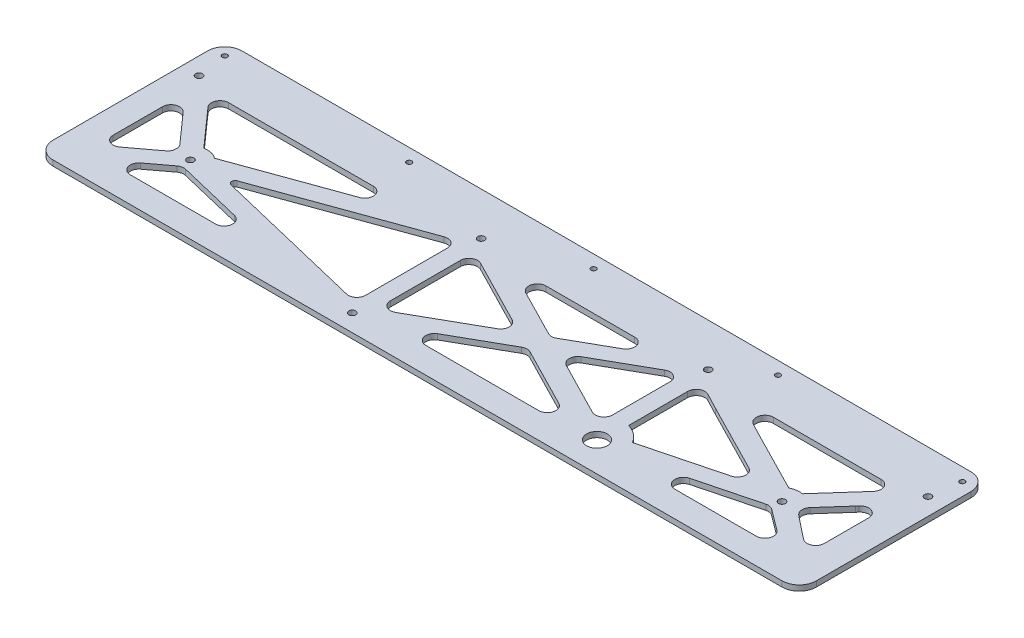
SolidWorks part; units mm, degrees
ref_plane "Front" through (0, 0, 0) normal (0, 0, 1) x (1, 0, 0)
ref_plane "Top" through (0, 0, 0) normal (0, 1, 0) x (1, 0, 0)
ref_plane "Right" through (0, 0, 0) normal (1, 0, 0) x (0, 0, -1)
sketch "Sketch1" plane through (0, 0, 0) normal (0, 1, 0) x (1, 0, 0)
  line L0 (-26.7996, 0) -> (-26.7996, 40)
  line L1 (-26.7996, 0) -> (417.7004, 0)
  line L2 (-26.7996, 0) -> (-26.7996, 110)
  line L3 (-26.7996, 110) -> (417.7004, 110)
  line L4 (417.7004, 0) -> (417.7004, 110)
  line L5 (-26.7996, 40) -> (23.2004, 40)
  line L6 (417.7004, 0) -> (417.7004, 40)
  line L7 (417.7004, 40) -> (367.7004, 40)
  line L8 (23.2004, 40) -> (103.2004, 40)
  line L9 (367.7004, 40) -> (191.7004, 40)
  line L10 (-26.7996, 110) -> (-26.7996, 85)
  line L11 (-26.7996, 85) -> (417.7004, 85)
  line L12 (-26.7996, 85) -> (-16.7996, 85)
  line L13 (417.7004, 85) -> (407.7004, 85)
  line L14 (103.2004, 40) -> (191.7004, 40)
  line L15 (147.4504, 40) -> (147.4504, 85)
  line L16 (279.7004, 40) -> (279.7004, 85)
  line L17 (147.4504, 40) -> (147.4504, 10)
  line L18 (-26.7996, 110) -> (-26.7996, 102.5)
  line L19 (-26.7996, 102.5) -> (417.7004, 102.5)
  line L20 (-26.7996, 102.5) -> (-19.2996, 102.5)
  line L21 (417.7004, 102.5) -> (410.2004, 102.5)
  line L22 (195.4504, 102.5) -> (410.2004, 102.5)
  line L23 (-19.2996, 102.5) -> (195.4504, 102.5)
  line L24 (417.7004, 0) -> (417.7004, 17.2282)
  line L25 (417.7004, 17.2282) -> (282.7004, 17.2282)
  circle A10 centre (367.7004, 40) radius 2
  circle A11 centre (23.2004, 40) radius 2
  circle A25 centre (-16.7996, 85) radius 2
  circle A26 centre (407.7004, 85) radius 2
  circle A27 centre (147.4504, 85) radius 2
  circle A28 centre (279.7004, 85) radius 2
  circle A29 centre (147.4504, 10) radius 2
  circle A30 centre (195.4504, 102.5) radius 1.5
  circle A31 centre (-19.2996, 102.5) radius 1.5
  circle A32 centre (410.2004, 102.5) radius 1.5
  circle A33 centre (302.8254, 102.5) radius 1.5
  circle A34 centre (88.0754, 102.5) radius 1.5
  circle A35 centre (282.7004, 17.2282) radius 6
  dimension "D3" = 40
  dimension "D7" = 80
  dimension "D8" = 176
  dimension "D9" = 25
  dimension "D11" = 10
  dimension "D12" = 30
  dimension "D13" = 7.5
  dimension "D14" = 7.5
  dimension "D16" = 17.2282
  dimension "D1" = 110
  dimension "D2" = 444.5
  dimension "D4" = 50
  dimension "D5" = 40
  dimension "D6" = 50
  dimension "D10" = 10
  dimension "D15" = 7.5
  dimension "D17" = 135
extrude "Boss-Extrude1" add sketch "Sketch1" along normal blind 3.175 contours A34 L23 A30 L22 A33 A32 L21 L4 L3 L10 L19 A31 | A34 L23 A31 L19 L2 L11 A25 A27 A28 A26 L13 L4 L21 A32 L22 A33 A30 | A27 L11 A25 L2 L5 A11 L8 L14 L15 | A28 L11 A27 L15 L14 L9 L16 | A28 L16 L9 A10 L7 L4 L13 A26 L11 | A35 L6 L7 A10 L9 L14 A29 L8 A11 L5 L0 L1 L4 region at (194.9253, 0, -20.0113) region at (60.3825, 0, -62.4913) region at (195.421, 0, -93.7571) region at (195.4504, 0, -106.2666) region at (348.6559, 0, -62.489) region at (213.5754, 0, -62.4771)
fillet "Fillet1" radius 10 4 edges at (417.7004, 1.5875, -110) (417.7004, 1.5875, 0) (-26.7996, 1.5875, 0) (-26.7996, 1.5875, -110)
sketch "Sketch2" plane through (0, 3.175, 0) normal (0, 1, 0) x (1, 0, 0)
  line L0 (23.2004, 40) -> (16.1294, 32.9289)
  line L1 (147.4504, 47.5) -> (152.4504, 47.5)
  line L2 (391.4375, 59.1782) -> (378.9401, 45.1187)
  line L3 (383.9634, 65.8218) -> (369.7169, 49.7946)
  line L4 (9732.2026, 3263.3975) -> (9728.9552, 3272.8555)
  line L5 (147.4504, 47.5) -> (142.4504, 47.5)
  line L6 (322.4478, 33.4546) -> (294.4087, 26.1989)
  line L7 (152.4504, 47.5) -> (152.4504, 67.9441)
  line L8 (-16.7996, 0) -> (407.7004, 0) construction
  line L9 (147.4504, 10) -> (147.4504, 0)
  line L10 (152.4504, 47.5) -> (152.4504, 27.2341)
  line L11 (142.4504, 47.5) -> (142.4504, 70.4046)
  line L12 (142.4504, 47.5) -> (142.4504, 22.7018)
  line L13 (147.4504, 10) -> (147.4504, 85)
  line L14 (147.4504, 85) -> (279.7004, 85)
  line L15 (279.7004, 85) -> (279.7004, 17.2282)
  line L16 (251.0087, 15) -> (185.2783, 15)
  line L17 (147.4504, 85) -> (-16.7996, 85)
  line L18 (-16.7996, 85) -> (23.2004, 40)
  line L19 (279.7004, 85) -> (407.7004, 85)
  line L20 (65.3254, 85) -> (65.3254, 80)
  line L21 (65.3254, 80) -> (5.4689, 80)
  line L22 (65.3254, 80) -> (89.687, 80)
  line L23 (190.2472, 80) -> (241.8726, 80)
  line L24 (322.713, 80) -> (385.432, 80)
  line L25 (279.7004, 51.1141) -> (274.7004, 51.1141)
  line L26 (279.7004, 51.1141) -> (284.7004, 51.1141)
  line L27 (274.7004, 51.1141) -> (274.7004, 34.284)
  line L28 (274.7004, 67.7659) -> (274.7004, 51.1141)
  line L29 (284.7004, 68.0769) -> (284.7004, 51.1141)
  line L30 (86.4989, 29.8603) -> (47.5547, 39.2634)
  line L31 (86.4989, 29.8603) -> (136.2769, 17.8415)
  line L32 (3.2004, 62.5) -> (6.9375, 65.8218)
  line L33 (23.2004, 40) -> (147.4504, 10)
  line L34 (85.3254, 25) -> (86.4989, 29.8603)
  line L35 (284.7004, 51.1141) -> (284.7004, 33.7148)
  line L36 (279.7004, 17.2282) -> (367.7004, 40)
  line L37 (367.7004, 40) -> (407.7004, 85)
  line L38 (383.9634, 65.8218) -> (389.169, 71.6782)
  line L39 (383.9634, 65.8218) -> (387.7004, 62.5)
  line L40 (391.4375, 59.1782) -> (387.7004, 62.5)
  line L41 (391.4375, 59.1782) -> (392.3703, 60.2665)
  line L42 (322.4478, 33.4546) -> (323.7004, 28.6141)
  line L43 (324.953, 23.7735) -> (323.7004, 28.6141)
  line L44 (329.0765, 24.8406) -> (364.2961, 33.9544)
  line L45 (322.4478, 33.4546) -> (340.0585, 38.0118)
  line L46 (324.953, 23.7735) -> (296.9139, 16.5178)
  line L47 (3.2004, 62.5) -> (-0.5366, 59.1782)
  line L48 (-0.5366, 59.1782) -> (12.2431, 44.801)
  line L49 (-0.5366, 59.1782) -> (-3.0625, 62.0198)
  line L50 (6.9375, 65.8218) -> (21.1839, 49.7946)
  line L51 (6.9375, 65.8218) -> (1.7318, 71.6782)
  line L52 (85.3254, 25) -> (84.1182, 20)
  line L53 (84.1182, 20) -> (26.4566, 33.9223)
  line L54 (30.3293, 32.9872) -> (63.9883, 24.8603)
  line L55 (330.3291, 15) -> (377.7004, 15)
  line L56 (407.7004, 10) -> (402.7004, 10)
  line L57 (401.1667, 31.1503) -> (401.1667, 57.0127)
  line L58 (367.7004, 40) -> (407.7004, 10)
  line L59 (390.7004, 29) -> (384.7004, 21)
  line L60 (23.2004, 40) -> (147.4504, 85)
  line L61 (83.5146, 67.5) -> (87.1363, 57.5)
  line L62 (83.5146, 67.5) -> (29.3522, 47.8839)
  line L63 (83.5146, 67.5) -> (91.3614, 70.2887)
  line L64 (87.1363, 57.5) -> (135.7478, 75.1058)
  line L65 (87.1363, 57.5) -> (47.3431, 43.088)
  line L66 (279.7004, 85) -> (367.7004, 40)
  line L67 (326.2572, 67.5) -> (321.1436, 57.5)
  line L68 (301.2048, 67.696) -> (341.0824, 47.304)
  line L69 (326.2572, 67.5) -> (320.3935, 70.5706)
  line L70 (326.2572, 67.5) -> (362.8903, 48.7672)
  line L71 (147.4504, 85) -> (279.7004, 17.2282)
  line L72 (218.7979, 42.1248) -> (253.2889, 24.4498)
  line L73 (216.1377, 56.1141) -> (211.0132, 46.1141)
  line L74 (197.4862, 53.046) -> (159.7307, 72.3939)
  line L75 (215.0566, 56.6681) -> (187.9669, 70.5502)
  line L76 (236.3682, 45.7469) -> (267.4201, 29.8343)
  line L77 (147.4504, 10) -> (279.7004, 85)
  line L78 (211.1089, 51.8493) -> (216.0419, 43.1507)
  line L79 (219.799, 56.7661) -> (244.3347, 70.6483)
  line L80 (236.1863, 54.5484) -> (267.2382, 72.1176)
  line L81 (197.6682, 44.2445) -> (159.9126, 22.8824)
  line L82 (214.0554, 42.0268) -> (182.8161, 24.3517)
  line L83 (-16.7996, 85) -> (-16.7996, 15)
  line L84 (-11.7996, 10) -> (147.4504, 10)
  line L85 (147.4504, 10) -> (402.7004, 10)
  line L86 (407.7004, 85) -> (407.7004, 15)
  line L87 (-16.7996, 10) -> (-16.7996, 15)
  line L88 (-16.7996, 10) -> (-11.7996, 10)
  line L89 (13.2004, 15) -> (62.8148, 15)
  line L90 (-11.7996, 30) -> (-11.7996, 58.698)
  line L91 (390.7004, 29) -> (379.559, 37.8883)
  line L92 (388.7004, 18) -> (380.7004, 24)
  line L93 (380.7004, 24) -> (368.5487, 33.1138)
  line L94 (390.7004, 29) -> (393.1667, 27.1503)
  line L95 (23.2004, 40) -> (-16.7996, 10)
  line L96 (0.2004, 29) -> (6.2004, 21)
  line L97 (11.506, 37.4792) -> (-3.7996, 26)
  line L98 (10.2004, 24) -> (22.2831, 33.062)
  line L100 (6.2004, 21) -> (-8.4662, 10)
  line L101 (301.2048, 67.696) -> (292.0202, 72.5062)
  arc A0 (-3.0625, 62.0198) -> (-11.7996, 58.698) centre (-6.7996, 58.698) ccw
  arc A3 (219.799, 56.7661) -> (215.0566, 56.6681) centre (217.3369, 61.1179) cw
  arc A4 (241.8726, 80) -> (244.3347, 70.6483) centre (241.8726, 75) cw
  circle A5 centre (147.4504, 85) radius 10
  arc A7 (190.2472, 80) -> (187.9669, 70.5502) centre (190.2472, 75) ccw
  circle A8 centre (279.7004, 85) radius 10
  arc A10 (5.4689, 80) -> (1.7318, 71.6782) centre (5.4689, 75) ccw
  arc A11 (89.687, 80) -> (91.3614, 70.2887) centre (89.687, 75) cw
  arc A12 (135.7478, 75.1058) -> (142.4504, 70.4046) centre (137.4504, 70.4046) cw
  arc A13 (142.4504, 22.7018) -> (136.2769, 17.8415) centre (137.4504, 22.7018) cw
  arc A14 (47.5547, 39.2634) -> (47.3431, 43.088) centre (48.0241, 41.2075) cw
  arc A15 (159.9126, 22.8824) -> (152.4504, 27.2341) centre (157.4504, 27.2341) cw
  arc A16 (197.6682, 44.2445) -> (197.4862, 53.046) centre (195.206, 48.5962) ccw
  arc A17 (159.7307, 72.3939) -> (152.4504, 67.9441) centre (157.4504, 67.9441) ccw
  arc A18 (274.7004, 34.284) -> (267.4201, 29.8343) centre (269.7004, 34.284) cw
  circle A19 centre (147.4504, 10) radius 10
  circle A21 centre (23.2004, 40) radius 10
  circle A22 centre (9732.2026, 3263.3975) radius 10
  circle A24 centre (-16.7996, 85) radius 10
  circle A25 centre (407.7004, 85) radius 10
  circle A26 centre (279.7004, 17.2282) radius 17.2282
  circle A27 centre (367.7004, 40) radius 10
  arc A28 (236.1863, 54.5484) -> (236.3682, 45.7469) centre (238.6485, 50.1967) ccw
  arc A29 (274.7004, 67.7659) -> (267.2382, 72.1176) centre (269.7004, 67.7659) ccw
  arc A30 (341.0824, 47.304) -> (340.0585, 38.0118) centre (338.8059, 42.8523) cw
  arc A31 (322.713, 80) -> (320.3935, 70.5706) centre (322.713, 75) ccw
  arc A32 (292.0202, 72.5062) -> (284.7004, 68.0769) centre (289.7004, 68.0769) ccw
  arc A33 (385.432, 80) -> (389.169, 71.6782) centre (385.432, 75) cw
  arc A34 (379.559, 37.8883) -> (378.9401, 45.1187) centre (382.6772, 41.7969) cw
  arc A35 (401.1667, 57.0127) -> (392.3703, 60.2665) centre (396.1667, 57.0127) ccw
  arc A36 (401.1667, 31.1503) -> (393.1667, 27.1503) centre (396.1667, 31.1503) cw
  arc A37 (377.7004, 15) -> (380.7004, 24) centre (377.7004, 20) ccw
  arc A38 (218.7979, 42.1248) -> (214.0554, 42.0268) centre (216.5176, 37.675) ccw
  arc A39 (182.8161, 24.3517) -> (185.2783, 15) centre (185.2783, 20) ccw
  arc A40 (251.0087, 15) -> (253.2889, 24.4498) centre (251.0087, 20) ccw
  arc A41 (11.506, 37.4792) -> (12.2431, 44.801) centre (8.506, 41.4792) ccw
  arc A42 (-3.7996, 26) -> (-11.7996, 30) centre (-6.7996, 30) cw
  arc A43 (13.2004, 15) -> (10.2004, 24) centre (13.2004, 20) cw
  arc A44 (62.8148, 15) -> (63.9883, 24.8603) centre (62.8148, 20) ccw
  arc A45 (329.0765, 24.8406) -> (330.3291, 15) centre (330.3291, 20) ccw
  arc A46 (-11.7996, 10) -> (-16.7996, 15) centre (-11.7996, 15) cw
  arc A47 (402.7004, 10) -> (407.7004, 15) centre (402.7004, 15) ccw
  arc A48 (26.4566, 33.9223) -> (22.2831, 33.062) centre (25.2831, 29.062) ccw
  arc A49 (368.5487, 33.1138) -> (364.2961, 33.9544) centre (365.5487, 29.1138) ccw
  point P84 (213.5754, 13.6141)
  point P91 (85.3254, 62.5)
  point P98 (323.7004, 62.5)
  point P100 (321.1436, 57.5)
  point P106 (213.5754, 51.1141)
  point P109 (213.5754, 47.5)
  point P114 (211.0132, 46.1141)
  point P115 (213.5754, 47.5)
  point P128 (387.7004, 25)
  point P135 (3.2004, 25)
  point P136 (0.2004, 29)
  point P173 (384.7004, 21)
  dimension "D7" = 5
  dimension "D2" = 5
  dimension "D9" = 5
  dimension "D20" = 10
  dimension "D22" = 5
  dimension "D16" = 5
  dimension "D17" = 5
  dimension "D23" = 5
  dimension "D24" = 5
  dimension "D25" = 5
  dimension "D26" = 5
  dimension "D27" = 5
  dimension "D28" = 2
  dimension "D29" = 5
  dimension "D30" = 5
  dimension "D31" = 5
  dimension "D32" = 5
  dimension "D33" = 5
  dimension "D34" = 5
  dimension "D35" = 5
  dimension "D36" = 5
  dimension "D37" = 5
  dimension "D38" = 5
  dimension "D39" = 5
  dimension "D40" = 5
  dimension "D13" = 5
  dimension "D41" = 5
  dimension "D42" = 5
  dimension "D43" = 5
  dimension "D44" = 5
  dimension "D45" = 5
  dimension "D19" = 5
  dimension "D18" = 5
  dimension "D46" = 5
  dimension "D10" = 5
  dimension "D47" = 5
  dimension "D48" = 5
  dimension "D49" = 5
  dimension "D50" = 5
  dimension "D1" = 10
  dimension "D6" = 5
  dimension "D3" = 5
  dimension "D4" = 5
  dimension "D5" = 5
  dimension "D8" = 5
  dimension "D11" = 5
  dimension "D12" = 5
  dimension "D14" = 10
  dimension "D15" = 10
  dimension "D21" = 10
extrude "Cut-Extrude1" cut sketch "Sketch2" against normal blind 10 contours A21 L62 L63 A11 L22 L21 A10 L51 L50 | A42 L97 A41 A21 L48 L49 A0 L90 | L89 A44 L53 A21 L98 A43 | L53 A48 L98 A21 | A14 L30 L31 A13 L12 L11 A12 L64 L65 | L74 A17 L7 L10 A15 L81 A16 | L23 A7 L75 A3 L79 A4 | L16 A40 L72 A38 L82 A39 | L28 A29 L80 A28 L76 A18 A26 L27 | L101 A32 L29 L35 A26 L6 L45 A30 L68 | A18 A26 | A33 L24 A31 L69 L70 A27 L3 L38 | L44 A45 L55 A37 L93 A27 | A36 L57 A35 L41 L2 A34 L91 L94 | L93 A49 L44 A45 L55 A37 region at (36.9296, 3.175, -22.103) region at (24.7671, 3.175, -31.9692) region at (43.3698, 3.175, -68.2948) region at (-2.1335, 3.175, -43.7439) region at (108.6161, 3.175, -44.8774) region at (170.1476, 3.175, -47.8878) region at (271.5408, 3.175, -31.1451) region at (259.0948, 3.175, -51.0247) region at (307.4149, 3.175, -47.5805) region at (356.407, 3.175, -68.4868) region at (392.0855, 3.175, -43.601) region at (354.9862, 3.175, -22.1013) region at (217.8598, 3.175, -25.0975) region at (216.2593, 3.175, -71.0892)
equation "\"width\"=8.66025"
equation "\"supw\"=5"
